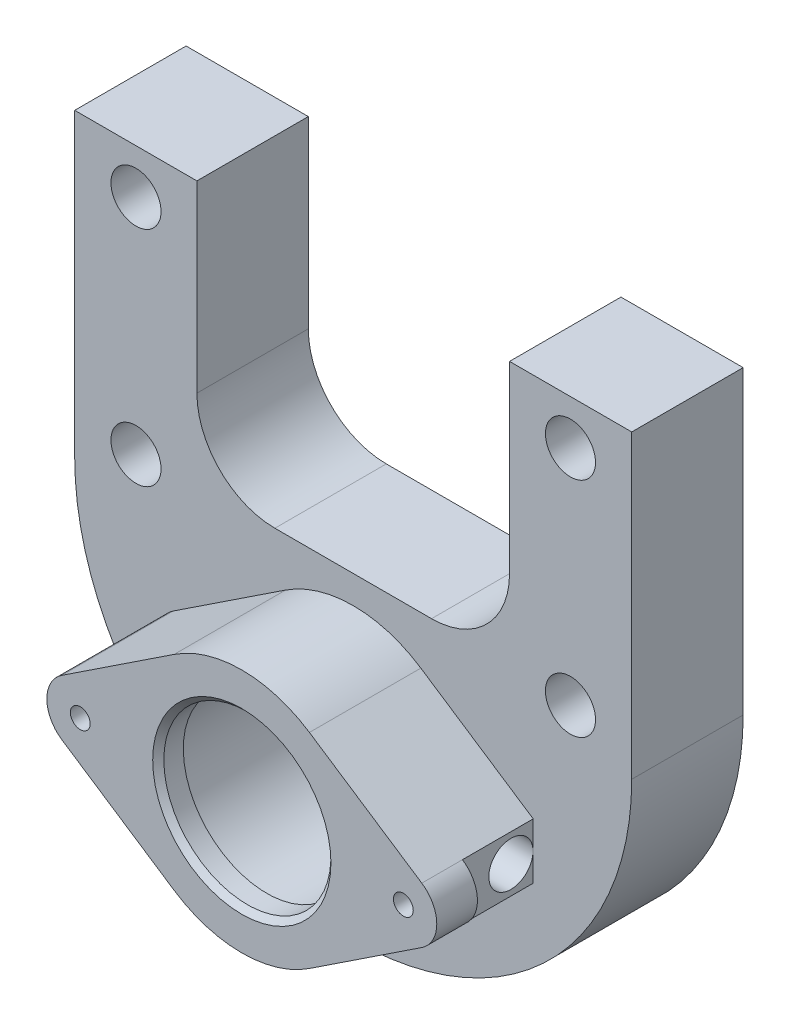
SolidWorks part; units mm, degrees
material "AISI 316 Annealed Stainless Steel Bar (SS)"
ref_plane "Front" through (0, 0, 0) normal (0, 0, 1) x (1, 0, 0)
ref_plane "Top" through (0, 0, 0) normal (0, 1, 0) x (1, 0, 0)
ref_plane "Right" through (0, 0, 0) normal (1, 0, 0) x (0, 0, -1)
sketch "Sketch1" plane through (0, 0, 0) normal (0, 0, 1) x (1, 0, 0)
  line L0 (0, 37) -> (0, 0) construction
  line L1 (-25, -15) -> (25, -15)
  line L2 (-25, -15) -> (-25, 37)
  line L3 (-25, 37) -> (25, 37)
  line L4 (25, -15) -> (25, 37)
  circle A0 centre (0, 0) radius 9.5 construction
  dimension "D3" = 19
  dimension "D5" = 15
  dimension "D1" = 52
  dimension "D2" = 50
extrude "Boss-Extrude1" add sketch "Sketch1" along normal blind 20
sketch "Sketch3" plane through (0, 0, 0) normal (1, 0, 0) x (0, 0, -1)
  line L0 (0, 0) -> (-20, 0)
  line L1 (-20, 0) -> (-20, 7.5)
  line L2 (-20, 7.5) -> (-17.75, 7.5)
  line L3 (-17.75, 7.5) -> (-17.75, 8)
  line L4 (-17.75, 8) -> (-7, 8)
  line L5 (-7, 8) -> (-7, 11)
  line L6 (-7, 11) -> (0, 11)
  line L7 (0, 37) -> (0, 0) construction
  line L8 (0, 11) -> (0, 0)
  line L9 (-20, -15) -> (-20, 37) construction
  dimension "D1" = 11
  dimension "D2" = 8
  dimension "D3" = 7.5
  dimension "D4" = 7
  dimension "D5" = 2.25
revolve "Cut-Revolve1" cut sketch "Sketch3" angle 360 about L0
hole_wizard "5/32 (0.15625) Diameter Hole1" positions "Sketch4" profile "Sketch5" hole size "5/32" standard "ANSI Inch" end condition up to next
sketch "Sketch4" plane through (25, 0, 0) normal (1, 0, 0) x (0, 0, -1)
  line L1 (0, 0) -> (-20, 0) construction
  line L2 (-20, -15) -> (-20, 37) construction
  point P0 (-12, 0)
  dimension "D1" = 8
sketch "Sketch5" plane through (25, 0, 12) normal (0, 1, 0) x (0, 0, -1)
  line L0 (0, 0) -> (0, 17)
  line L1 (0, 17) -> (1.9844, 17)
  line L2 (1.9844, 17) -> (1.9844, 0)
  line L5 (1.9844, 0) -> (0, 0)
  line L11 (0, -6.35) -> (0, 107.95) construction
  dimension "Thru Hole Dia." = 3.9688
  dimension "Thru Hole Depth" = 17
fillet "Fillet1" radius 5 1 edges at (0, 37, 20) profile chamfer
hole_wizard "#2-56 Tapped Hole1" positions "Sketch8" profile "Sketch9" tap size "#2-56" standard "ANSI Inch"
sketch "Sketch8" plane through (0, 0, 20) normal (0, 0, 1) x (1, 0, 0)
  line L0 (-14.5, 0) -> (14.5, 0)
  point P0 (-14.5, 0)
  point P2 (14.5, 0)
  dimension "D1" = 29
sketch "Sketch9" plane through (-14.5, 0, 20) normal (1, 0, 0) x (0, -1, 0)
  line L0 (0, 0) -> (0, 8.4542)
  line L1 (0, 8.4542) -> (0.889, 7.92)
  line L2 (0.889, 7.92) -> (0.889, 0)
  line L5 (0.889, 0) -> (0, 0)
  line L10 (0, 8.4542) -> (-0.889, 7.92) construction
  line L11 (0, -6.35) -> (0, 107.95) construction
  dimension "Tap Drill Dia." = 1.778
  dimension "Tap Drill Depth" = 7.92
  dimension "Drill Angle" = 118
cosmetic thread "Hole Thread1" parameters "D1"=6.2259, "D2"=2.1844
cosmetic thread "Hole Thread2" parameters "D1"=6.555, "D2"=2.1844
sketch "Sketch27" plane through (0, 0, 20) normal (0, 0, 1) x (1, 0, 0)
  line L0 (-16.1552, 2.5021) -> (-6.069, 9.1743)
  line L1 (6.069, 9.1743) -> (16.1552, 2.5021)
  line L2 (16.1552, -2.5021) -> (6.069, -9.1743)
  line L3 (-6.069, -9.1743) -> (-16.1552, -2.5021)
  arc A0 (-6.069, -9.1743) -> (6.069, -9.1743) centre (0, 0) ccw
  arc A1 (-16.1552, 2.5021) -> (-16.1552, -2.5021) centre (-14.5, 0) ccw
  arc A2 (16.1552, -2.5021) -> (16.1552, 2.5021) centre (14.5, 0) ccw
  arc A3 (6.069, 9.1743) -> (-6.069, 9.1743) centre (0, 0) ccw
  dimension "D1" = 11
  dimension "D2" = 3
extrude "Cut-Extrude6" cut sketch "Sketch27" against normal blind 10 flip side to cut
ref_plane "Plane1" through (17.5, 0, 0) normal (1, 0, 0) x (0, 0, -1)
hole_wizard "#8 Clearance Hole1" positions "Sketch20" profile "Sketch21" hole size "#8" standard "ANSI Inch" end condition through all
sketch "Sketch20" plane through (0, 0, 10) normal (0, 0, 1) x (1, 0, 0)
  line L0 (-19.5, 37) -> (-19.5, 33) construction
  line L1 (25, 37) -> (-25, 37) construction
  line L2 (-19.5, 33) -> (19.5, 33) construction
  line L3 (19.5, 33) -> (19.5, 37) construction
  line L6 (0, 33) -> (0, 37) construction
  line L9 (-19.5, 33) -> (-19.5, 13) construction
  line L10 (-19.5, 13) -> (19.5, 13) construction
  line L11 (19.5, 13) -> (19.5, 33) construction
  point P0 (19.5, 33)
  point P5 (-19.5, 33)
  point P36 (-19.5, 13)
  point P39 (19.5, 13)
  dimension "D1" = 39
  dimension "D2" = 4
  dimension "D3" = 20
sketch "Sketch21" plane through (19.5, 33, 10) normal (1, 0, 0) x (0, -1, 0)
  line L0 (0, 0) -> (0, 10)
  line L1 (0, 10) -> (2.2479, 10)
  line L2 (2.2479, 10) -> (2.2479, 0)
  line L5 (2.2479, 0) -> (0, 0)
  line L11 (0, -6.35) -> (0, 107.95) construction
  dimension "Thru Hole Dia." = 4.4958
  dimension "Thru Hole Depth" = 10
hole_wizard "1/8 (0.1250) Dowel Hole1" positions "Sketch10" profile "Sketch11" hole size "1/8" standard "ANSI Inch"
sketch "Sketch10" plane through (0, 0, 0) normal (0, 0, -1) x (-1, 0, 0)
  line L11 (-19.5, 13) -> (-19.5, 33) construction
  point P0 (-19.5, 23)
sketch "Sketch11" plane through (19.5, 23, 0) normal (1, 0, 0) x (0, 1, 0)
  line L0 (0, 0) -> (0, 5.9539)
  line L1 (0, 5.9539) -> (1.5875, 5)
  line L2 (1.5875, 5) -> (1.5875, 0)
  line L5 (1.5875, 0) -> (0, 0)
  line L10 (0, 5.9539) -> (-1.5875, 5) construction
  line L11 (0, -6.35) -> (0, 107.95) construction
  dimension "Hole Dia." = 3.175
  dimension "Hole Depth" = 5
  dimension "Drill Angle" = 118
hole_wizard "1/8 (0.1250) Dowel Slot1" positions "Sketch12" profile "Sketch13" size "1/8" standard "ANSI Inch" slot yes
sketch "Sketch12" plane through (0, 0, 0) normal (0, 0, -1) x (-1, 0, 0)
  line L0 (17.5, 23) -> (21.5, 23) construction
  line L6 (19.5, 33) -> (19.5, 13) construction
  point P0 (19.5, 23)
  dimension "D1" = 4
sketch "Sketch13" plane through (-19.5, 23, 0) normal (1, 0, 0) x (0, 1, 0)
  line L0 (0, 0) -> (0, 5.9539)
  line L1 (0, 5.9539) -> (1.5875, 5)
  line L2 (1.5875, 5) -> (1.5875, 0)
  line L5 (1.5875, 0) -> (0, 0)
  line L10 (0, 5.9539) -> (-1.5875, 5) construction
  line L11 (0, -6.35) -> (0, 107.95) construction
  dimension "Hole Dia." = 3.175
  dimension "Hole Depth" = 5
  dimension "Drill Angle" = 118
sketch "Sketch22" plane through (0, 0, 0) normal (0, 0, -1) x (-1, 0, 0)
  circle A0 centre (0, 0) radius 10
  dimension "D1" = 20
chamfer "Chamfer1" distance 0.5 angle 45 2 edges at (0, 11, 0) (0, 7.5, 20)
sketch "Sketch24" plane through (0, 0, 20) normal (0, 0, 1) x (1, 0, 0)
  line L1 (-14.0313, 37) -> (14.0313, 37)
  line L2 (-14.0313, 37) -> (-14.0313, 20.5)
  line L3 (-7.0313, 13.5) -> (7.0313, 13.5)
  line L4 (14.0313, 37) -> (14.0313, 20.5)
  line L5 (0, 13.5) -> (0, 0) construction
  line L6 (25, 37) -> (-25, 37) construction
  arc A1 (7.0313, 13.5) -> (14.0313, 20.5) centre (7.0313, 20.5) ccw
  arc A2 (-14.0313, 20.5) -> (-7.0313, 13.5) centre (-7.0313, 20.5) ccw
  circle A3 centre (-19.5, 33) radius 2.2479 construction
  circle A4 centre (0, 0) radius 11.5 construction
  dimension "D2" = 7
  dimension "D4" = 3.2208
  dimension "D3" = 2
extrude "Cut-Extrude5" cut sketch "Sketch24" against normal through all
fillet "Fillet3" radius 25 2 edges at (25, -15, 5) (-25, -15, 5)
sketch "Sketch28" plane through (17.5, 0, 0) normal (1, 0, 0) x (0, 0, -1)
  line L1 (-10, 2.5021) -> (-16.35, 2.5021)
  line L2 (-10, 2.5021) -> (-10, -2.5021)
  line L3 (-10, -2.5021) -> (-16.35, -2.5021)
  line L4 (-16.35, 2.5021) -> (-16.35, -2.5021)
  line L5 (-20, 0) -> (-16.35, 0) construction
  line L6 (-20, 2.5021) -> (-20, -2.5021) construction
  line L7 (-10, 2.5021) -> (-20, 2.5021) construction
  line L8 (-10, -2.5021) -> (-20, -2.5021) construction
  line L9 (-10, 10) -> (-10, 37) construction
  dimension "D1" = 6.35
extrude "Cut-Extrude7" cut sketch "Sketch28" against normal up to vertex (1.3448 mm away) up to point (16.1552, 2.5021, 20)
